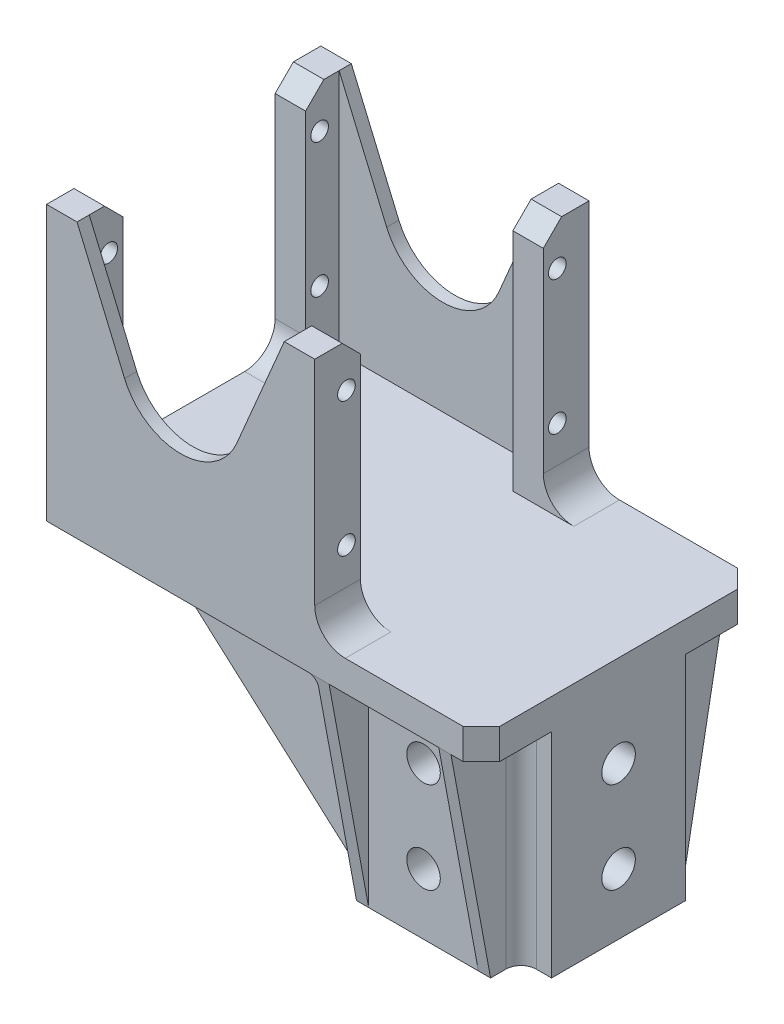
SolidWorks part; units mm, degrees
material "PLA"
ref_plane "Front Plane" through (0, 0, 0) normal (0, 0, 1) x (1, 0, 0)
ref_plane "Top Plane" through (0, 0, 0) normal (0, 1, 0) x (1, 0, 0)
ref_plane "Right Plane" through (0, 0, 0) normal (1, 0, 0) x (0, 0, -1)
sketch "Sketch2" plane through (0, 0, 0) normal (0, 0, 1) x (1, 0, 0)
  line L0 (12.8375, 22.5) -> (17.8375, 22.5) construction
  line L1 (-53.5125, 22.5) -> (17.8375, 22.5) construction
  line L2 (-17.8375, 22.5) -> (-17.8375, -22.5) construction
  line L3 (-53.5125, -22.5) -> (17.8375, -22.5)
  line L4 (17.8375, 22.5) -> (17.8375, -22.5) construction
  line L5 (-17.8375, 22.5) -> (17.8375, -22.5) construction
  line L6 (-17.8375, -22.5) -> (17.8375, 22.5) construction
  line L7 (-48.5125, 22.5) -> (12.8375, 22.5) construction
  line L8 (-17.8375, 22.5) -> (-17.8375, -17.5) construction
  line L9 (-48.5125, -17.5) -> (12.8375, -17.5) construction
  line L10 (12.8375, 22.5) -> (12.8375, -17.5) construction
  line L11 (-17.8375, 22.5) -> (12.8375, -17.5) construction
  line L12 (-17.8375, -17.5) -> (12.8375, 22.5) construction
  line L14 (-17.8375, -17.5) -> (-48.5125, 22.5) construction
  line L15 (-17.8375, 22.5) -> (-48.5125, -17.5) construction
  line L16 (-17.8375, -22.5) -> (-53.5125, 22.5) construction
  line L17 (-17.8375, 22.5) -> (-53.5125, -22.5) construction
  line L18 (-48.5125, 22.5) -> (-48.5125, -17.5)
  line L19 (-53.5125, 22.5) -> (-53.5125, -22.5)
  line L20 (-48.5125, 22.5) -> (-53.5125, 22.5)
  line L22 (-9.5125, -17.5) -> (-9.5125, 22.5)
  line L23 (-9.5125, 22.5) -> (-14.5125, 22.5)
  line L24 (-14.5125, 22.5) -> (-14.5125, -17.5)
  line L26 (17.8375, -17.5) -> (17.8375, -22.5)
  line L27 (-48.5125, -17.5) -> (-14.5125, -17.5)
  line L28 (-9.5125, -17.5) -> (17.8375, -17.5)
  point P4 (0, 0)
  point P8 (-2.5, 2.5)
  point P14 (-33.175, 2.5)
  point P15 (-35.675, 0)
  dimension "D1" = 5
  dimension "D2" = 40
  dimension "D3" = 27.35
  dimension "D4" = 5
  dimension "D5" = 34
  dimension "D6" = 5
extrude "Boss-Extrude1" add sketch "Sketch2" along normal blind 45
sketch "Sketch3" plane through (-53.5125, 0, 0) normal (1, 0, 0) x (0, 0, -1)
  line L0 (-5.2, 22.5) -> (-5.2, -22.5) construction
  line L2 (-39.8, 22.5) -> (-39.8, -22.5) construction
  line L4 (-37.5, 22.5) -> (-7.5, 22.5)
  line L5 (-37.5, 22.5) -> (-37.5, -17.5)
  line L6 (-37.5, -17.5) -> (-7.5, -17.5)
  line L7 (-7.5, 22.5) -> (-7.5, -17.5)
  line L8 (-37.5, 22.5) -> (-7.5, -17.5) construction
  line L9 (-37.5, -17.5) -> (-7.5, 22.5) construction
  line L10 (-45, 22.5) -> (0, 22.5) construction
  line L11 (-39.8, 15.5) -> (-5.2, 15.5) construction
  line L12 (-39.8, -6.5) -> (-5.2, -6.5) construction
  line L13 (-45, -22.5) -> (0, -22.5) construction
  circle A2 centre (-5.2, 15.5) radius 1.25 construction
  circle A3 centre (-5.2, -6.5) radius 1.25 construction
  circle A4 centre (-39.8, 15.5) radius 1.25 construction
  circle A5 centre (-39.8, -6.5) radius 1.25 construction
  point P10 (-22.5, 2.5)
  dimension "D4" = 2.3
  dimension "D7" = 2.5
  dimension "D5" = 2.5
  dimension "D6" = 2.5
  dimension "D9" = 2.5
  dimension "D8" = 22
  dimension "D1" = 30
  dimension "D2" = 5
  dimension "D3" = 2.3
  dimension "D10" = 11
extrude "Cut-Extrude1" cut sketch "Sketch3" along normal through all
sketch "Sketch4" plane through (0, -22.5, 0) normal (0, -1, 0) x (1, 0, 0)
  line L0 (-53.5125, 22.5) -> (17.8375, 22.5) construction
  line L1 (17.8375, 45) -> (17.8375, 0) construction
  line L3 (-53.5125, 45) -> (-53.5125, 0) construction
  line L10 (-8.4125, 32.75) -> (12.0875, 32.75)
  line L11 (-8.4125, 32.75) -> (-8.4125, 12.25)
  line L12 (-8.4125, 12.25) -> (12.0875, 12.25)
  line L13 (12.0875, 32.75) -> (12.0875, 12.25)
  line L14 (-8.4125, 32.75) -> (12.0875, 12.25) construction
  line L15 (-8.4125, 12.25) -> (12.0875, 32.75) construction
  line L16 (-14.1625, 38.5) -> (17.8375, 38.5)
  line L17 (-14.1625, 38.5) -> (-14.1625, 6.5)
  line L18 (-14.1625, 6.5) -> (17.8375, 6.5)
  line L19 (17.8375, 38.5) -> (17.8375, 6.5)
  line L20 (-14.1625, 38.5) -> (17.8375, 6.5) construction
  line L21 (-14.1625, 6.5) -> (17.8375, 38.5) construction
  circle A0 centre (1.8375, 22.5) radius 2.5
  point P18 (1.8375, 22.5)
  point P23 (1.8375, 22.5)
  dimension "D1" = 5
  dimension "D2" = 20.5
  dimension "D3" = 20.5
  dimension "D4" = 32
extrude "Boss-Extrude2" add sketch "Sketch4" along normal blind 35 contours L19 L16 L17 L18 L10 L13 L12 L11 region at (1.8375, -22.5, 38.0475)
sketch "Sketch5" plane through (0, 0, 38.5) normal (0, 0, 1) x (1, 0, 0)
  line L0 (1.8375, -22.5) -> (1.8375, -57.5) construction
  line L3 (-14.1625, -22.5) -> (17.8375, -22.5) construction
  line L4 (-14.1625, -57.5) -> (17.8375, -57.5) construction
  circle A0 centre (1.8375, -32.5) radius 2.5 construction
  circle A1 centre (1.8375, -47.5) radius 2.5 construction
  dimension "D2" = 5
  dimension "D3" = 5
  dimension "D4" = 10
  dimension "D1" = 15
sketch "Sketch6" plane through (0, -57.5, 0) normal (0, -1, 0) x (-1, 0, 0)
  line L1 (14.1625, -38.5) -> (9.1625, -38.5)
  line L2 (14.1625, -38.5) -> (14.1625, -33.5)
  line L3 (14.1625, -33.5) -> (9.1625, -33.5)
  line L4 (9.1625, -38.5) -> (9.1625, -33.5)
  line L5 (14.1625, -38.5) -> (9.1625, -33.5) construction
  line L6 (14.1625, -33.5) -> (9.1625, -38.5) construction
  line L7 (-17.8375, -38.5) -> (-12.8375, -38.5)
  line L8 (-17.8375, -38.5) -> (-17.8375, -33.5)
  line L9 (-17.8375, -33.5) -> (-12.8375, -33.5)
  line L10 (-12.8375, -38.5) -> (-12.8375, -33.5)
  line L11 (-17.8375, -38.5) -> (-12.8375, -33.5) construction
  line L12 (-17.8375, -33.5) -> (-12.8375, -38.5) construction
  line L13 (-17.8375, -6.5) -> (-12.8375, -6.5)
  line L14 (-17.8375, -6.5) -> (-17.8375, -11.5)
  line L15 (-17.8375, -11.5) -> (-12.8375, -11.5)
  line L16 (-12.8375, -6.5) -> (-12.8375, -11.5)
  line L17 (-17.8375, -6.5) -> (-12.8375, -11.5) construction
  line L18 (-17.8375, -11.5) -> (-12.8375, -6.5) construction
  line L19 (14.1625, -6.5) -> (9.1625, -6.5)
  line L20 (14.1625, -6.5) -> (14.1625, -11.5)
  line L21 (14.1625, -11.5) -> (9.1625, -11.5)
  line L22 (9.1625, -6.5) -> (9.1625, -11.5)
  line L23 (14.1625, -6.5) -> (9.1625, -11.5) construction
  line L24 (14.1625, -11.5) -> (9.1625, -6.5) construction
  point P4 (11.6625, -36)
  point P11 (-15.3375, -36)
  point P18 (-15.3375, -9)
  point P25 (11.6625, -9)
  dimension "D1" = 5
  dimension "D2" = 5
  dimension "D3" = 5
  dimension "D4" = 5
extrude "Cut-Extrude4" cut sketch "Sketch6" against normal up to surface (35 mm away) up to face at (-8, -22.5, 22.5)
sketch "Sketch9" plane through (0, 0, 33.5) normal (0, 0, 1) x (1, 0, 0)
  line L0 (-14.1625, -57.5) -> (-53.5125, -22.5)
  line L1 (-53.5125, -22.5) -> (17.8375, -22.5) construction
  line L2 (-53.5125, -22.5) -> (17.8375, -22.5) construction
rib "Rib1" sketch "Sketch9" sketch "Sketch9" thickness 2 extrusion direction parallel to sketch draft on no parameters "D1"=2
pattern_linear "LPattern1" count 2 spacing 20 along (0, 0, -1) of "Rib1"
sketch "Sketch14" plane through (12.8375, 0, 0) normal (1, 0, 0) x (0, 0, -1)
  line L0 (-6.5, -57.5) -> (0, -22.5)
rib "Rib6" sketch "Sketch14" sketch "Sketch14" thickness 2 extrusion direction parallel to sketch draft on no parameters "D1"=2
sketch "Sketch15" plane through (-9.1625, 0, 0) normal (-1, 0, 0) x (0, 0, 1)
  line L0 (6.5, -57.5) -> (0, -22.5)
rib "Rib7" sketch "Sketch15" sketch "Sketch15" thickness 2 extrusion direction parallel to sketch draft on no parameters "D1"=2
fillet "Fillet2" radius 5 3 edges at (-14.1625, -22.5, 22.5) (1.8375, -22.5, 6.5) (1.8375, -22.5, 38.5)
fillet "Fillet3" radius 5 2 edges at (-9.5125, -17.5, 3.75) (-9.5125, -17.5, 41.25)
sketch "Sketch17" plane through (0, 0, 45) normal (0, 0, 1) x (1, 0, 0)
  line L0 (-48.5125, 22.5) -> (-31.5125, -17.5)
  line L1 (-14.5125, -17.5) -> (-48.5125, -17.5) construction
rib "Rib10" sketch "Sketch17" sketch "Sketch17" thickness 2 extrusion direction parallel to sketch draft on no parameters "D1"=2
sketch "Sketch18" plane through (0, 0, 45) normal (0, 0, 1) x (1, 0, 0)
  line L0 (-31.5125, -17.5) -> (-14.5125, 22.5)
rib "Rib11" sketch "Sketch18" sketch "Sketch18" thickness 2 extrusion direction parallel to sketch draft on no parameters "D1"=2
fillet "Fillet4" radius 10 1 edges at (-31.5125, -17.5, 44)
pattern_linear "LPattern2" count 2 spacing 43 along (0, 0, -1) of "Fillet4", "Rib11", "Rib10"
hole_wizard "M5 Clearance Hole2" positions "Sketch20" profile "Sketch22" hole size "M5" standard "ISO"
sketch "Sketch20" plane through (0, 0, 38.5) normal (0, 0, 1) x (1, 0, 0)
  point P0 (1.8375, -32.5)
  point P3 (1.8375, -47.5)
sketch "Sketch22" plane through (1.8375, -32.5, 38.5) normal (1, 0, 0) x (0, -1, 0)
  line L0 (0, 0) -> (0, 7.6524)
  line L1 (0, 7.6524) -> (2.75, 6)
  line L2 (2.75, 6) -> (2.75, 0)
  line L5 (2.75, 0) -> (0, 0)
  line L10 (0, 7.6524) -> (-2.75, 6) construction
  line L11 (0, -6.35) -> (0, 107.95) construction
  dimension "Hole Dia." = 5.5
  dimension "Hole Depth" = 6
  dimension "Drill Angle" = 118
hole_wizard "M2.5 Clearance Hole1" positions "Sketch23" profile "Sketch24" hole size "M2.5" standard "ISO" end condition through all
sketch "Sketch23" plane through (-53.5125, 0, 0) normal (-1, 0, 0) x (0, 0, 1)
  point P0 (5.2, 15.5)
  point P3 (39.8, 15.5)
  point P6 (39.8, -6.5)
  point P9 (5.2, -6.5)
sketch "Sketch24" plane through (-53.5125, 15.5, 5.2) normal (0, 1, 0) x (0, 0, 1)
  line L0 (0, 0) -> (0, 71.35)
  line L1 (0, 71.35) -> (1.45, 71.35)
  line L2 (1.45, 71.35) -> (1.45, 0)
  line L5 (1.45, 0) -> (0, 0)
  line L11 (0, -6.35) -> (0, 107.95) construction
  dimension "Thru Hole Dia." = 2.9
  dimension "Thru Hole Depth" = 71.35
fillet "Fillet5" radius 2.5 4 edges at (-9.1625, -40, 11.5) (-9.1625, -40, 33.5) (12.8375, -40, 33.5) (12.8375, -40, 11.5)
extrude "Boss-Extrude4" add sketch "Sketch4<4>" along normal blind 8 contours A0 region at (1.8375, -22.5, 22.5)
sketch "Sketch4<4>" plane through (0, -22.5, 0) normal (0, -1, 0) x (1, 0, 0) same geometry as "Sketch4"
pattern_circular "CirPattern1" count 4 every 90 about axis through (1.8375, -30.5, 22.5) along (0, -1, 0) of "M5 Clearance Hole2"
ref_axis "Axis2" through (1.8375, -30.5, 22.5) along (0, 1, 0)
ref_plane "Plane1" through (0, 0, 22.5) normal (0, 0, 1) x (1, 0, 0)
mirror "Mirror1" about plane through (0, 0, 22.5) normal (0, 0, 1) of "Rib6", "Rib7"
chamfer "Chamfer1" distance 3 angle 45 6 edges at (17.8375, -20, 0) (17.8375, -20, 45) (-51.0125, 22.5, 37.5) (-51.0125, 22.5, 7.5) (-12.0125, 22.5, 7.5) (-12.0125, 22.5, 37.5)
fillet "Fillet6" radius 5 2 edges at (-51.0125, -17.5, 37.5) (-51.0125, -17.5, 7.5)
fillet "Fillet7" radius 1.5 12 edges at (-9.1625, -22.5, 4.5) (-9.8947, -22.5, 10.7678) (-14.1625, -42.5, 13.5) (-15.627, -23.9645, 13.5) (-14.1625, -42.5, 31.5) (-15.627, -23.9645, 31.5) (-9.1625, -22.5, 40.5) (-9.8947, -22.5, 34.2322) (-32.5875, -22.5, 11.5) (-36.3375, -22.5, 13.5) (-36.3375, -22.5, 31.5) (-32.5875, -22.5, 33.5)
sketch "Sketch27" plane through (0, 0, 45) normal (0, 0, 1) x (1, 0, 0)
  line L0 (17.8375, -17.5) -> (17.8375, -22.5) construction
  line L1 (-9.5125, -12.5) -> (17.8375, -12.5)
  line L2 (-9.5125, -12.5) -> (-9.5125, -18.2)
  line L3 (-9.5125, -18.2) -> (17.8375, -18.2)
  line L4 (17.8375, -12.5) -> (17.8375, -18.2)
  line L5 (10.8375, -22.5) -> (12.8375, -22.5) construction
  dimension "D1" = 4.3
